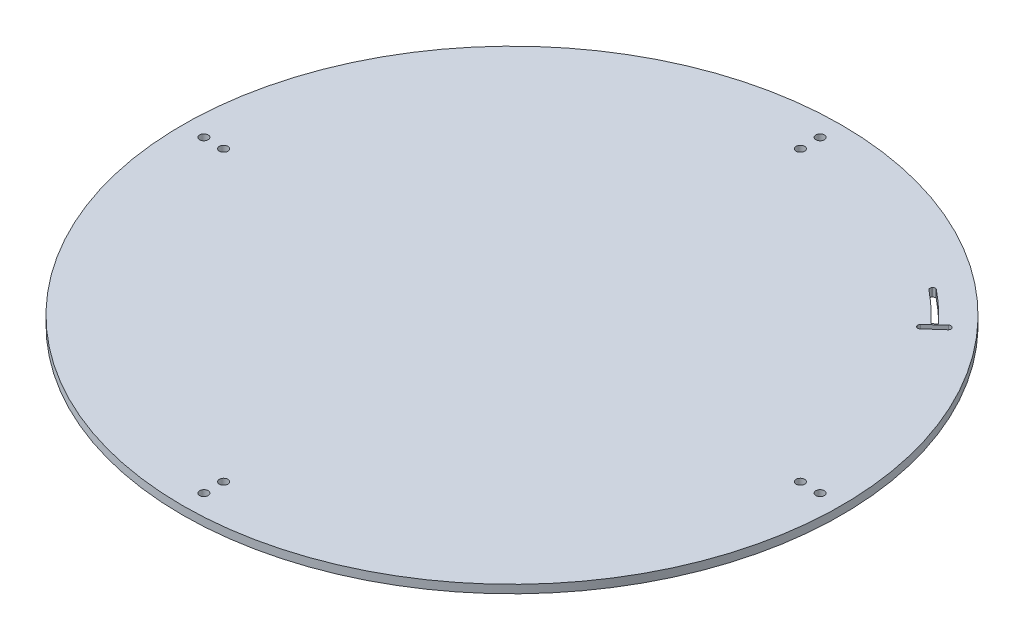
SolidWorks part; units mm, degrees
ref_plane "前视基准面" through (0, 0, 0) normal (0, 0, 1) x (1, 0, 0)
ref_plane "上视基准面" through (0, 0, 0) normal (0, 1, 0) x (1, 0, 0)
ref_plane "右视基准面" through (0, 0, 0) normal (1, 0, 0) x (0, 0, -1)
ref_axis "中心轴" through (0, -55, 0) along (0, 1, 0)
sketch "草图1" plane through (0, 0, 0) normal (0, 1, 0) x (1, 0, 0)
  circle A0 centre (0, 0) radius 200
extrude "主体" add sketch "草图1" along normal blind 5
sketch "草图2" plane through (0, 5, 0) normal (0, 1, 0) x (1, 0, 0)
  line L0 (0, 0) -> (0, 120.98) construction
  circle A0 centre (0, 0) radius 200
  circle A1 centre (0, 0) radius 187 construction
  circle A2 centre (0, 0) radius 200 construction
  circle A3 centre (0, 0) radius 175 construction
  circle A6 centre (0, -175) radius 2.6
  circle A7 centre (0, -187) radius 2.6
extrude "切除-拉伸3" cut sketch "草图2" against normal up to next contours A6 | A7 region at (0, 5, 175) region at (0, 5, 187)
pattern_circular "阵列(圆周)1" count 4 over 360 about axis through (0, -55, 0) along (0, 1, 0) of "切除-拉伸3"
sketch "草图4" plane through (0, 0, 0) normal (0.682, 0, 0.7314) x (0.7314, 0, -0.682)
  line L0 (180, -3) -> (187.114, -3) construction
  line L1 (180, 9) -> (183, 9) construction
  line L2 (180, 9) -> (180, -3) construction
  line L3 (180, -3) -> (183, -3) construction
  line L4 (183, 9) -> (183, -3) construction
  line L5 (183.1, 9.1) -> (183.1, -3.1)
  line L6 (179.9, -3.1) -> (183.1, -3.1)
  line L7 (179.9, 9.1) -> (179.9, -3.1)
  line L8 (179.9, 9.1) -> (183.1, 9.1)
  line L11 (180, 10.5) -> (180, -3) construction
  line L12 (183, 10.5) -> (183, 0) construction
  dimension "D1" = 0.1
revolve "切除-旋转3" cut sketch "草图4" angle 8.5 about axis through (0, -55, 0) along (0, 1, 0)
fillet "圆角2" radius 1.5 2 edges at (111.9904, 2.5, -140.7912) (113.9824, 2.5, -143.2956)
sketch "草图6" plane through (0, 5, 0) normal (0, 1, 0) x (1, 0, 0)
  line L0 (127.7881, 118.027) -> (138.8043, 128.2018) construction
  line L4 (141.0206, 125.7598) -> (129.8285, 115.7789) construction
  line L5 (130.9772, 116.8032) -> (139.9335, 124.7903) construction
  line L7 (128.9187, 119.0713) -> (137.7343, 127.2135) construction
  line L8 (127.6468, 118.0326) -> (138.8099, 128.343)
  line L9 (141.1618, 125.7517) -> (129.8204, 115.6376)
  arc A0 (141.0206, 125.7598) -> (138.8043, 128.2018) centre (0, 0) ccw construction
  arc A1 (129.8285, 115.7789) -> (127.7881, 118.027) centre (0, 0) ccw construction
  arc A4 (141.1618, 125.7517) -> (138.8099, 128.343) centre (0, 0) ccw
  arc A5 (129.8204, 115.6376) -> (127.6468, 118.0326) centre (0, 0) ccw
  dimension "D1" = 0.1
extrude "开孔" cut sketch "草图6" against normal up to next
fillet "圆角1" radius 1.5 4 edges at (129.8204, 2.5, -115.6376) (141.1618, 2.5, -125.7517) (138.8099, 2.5, -128.343) (127.6468, 2.5, -118.0326)
